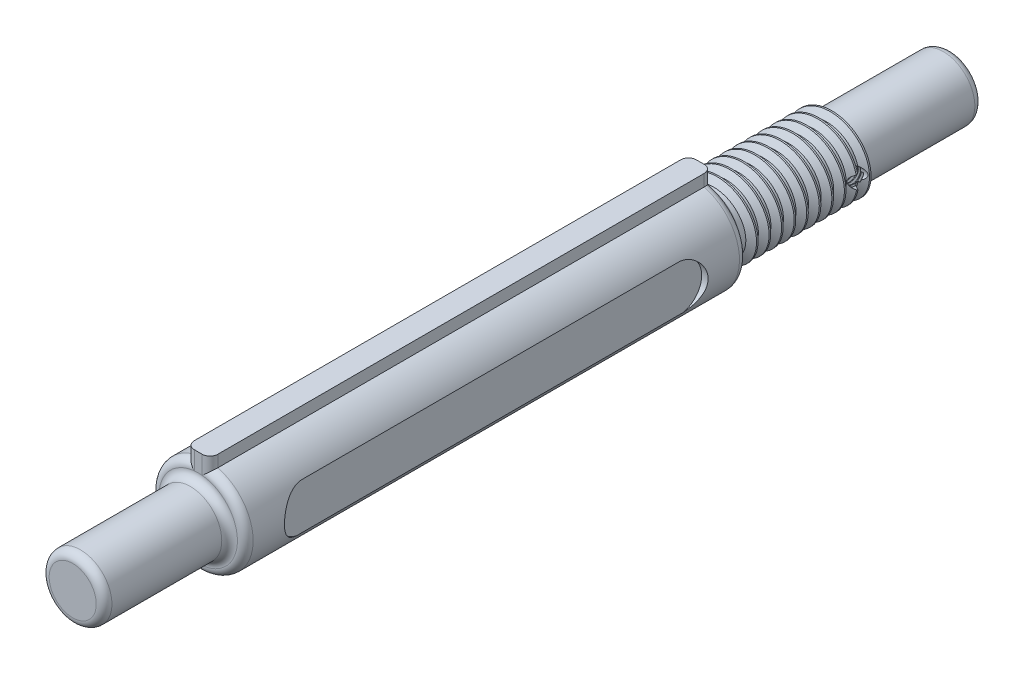
SolidWorks part; units mm, degrees
material "AISI 1020"
ref_plane "Front Plane" through (0, 0, 0) normal (0, 0, 1) x (1, 0, 0)
ref_plane "Top Plane" through (0, 0, 0) normal (0, 1, 0) x (1, 0, 0)
ref_plane "Right Plane" through (0, 0, 0) normal (1, 0, 0) x (0, 0, -1)
sketch "Sketch1" plane through (0, 0, 0) normal (0, 0, 1) x (1, 0, 0)
  line L0 (-1.1906, 4.6113) -> (-1.1906, 5.8019)
  line L1 (-1.1906, 5.8019) -> (1.1906, 5.8019)
  line L2 (1.1906, 5.8019) -> (1.1906, 4.6113)
  arc A1 (-1.1906, 4.6113) -> (1.1906, 4.6113) centre (0, 0) ccw
  point P2 (0, 5.8019)
  dimension "D1" = 4.7625
  dimension "D2" = 1.1906
  dimension "D3" = 2.3813
extrude "Boss-Extrude1" add sketch "Sketch1" along normal blind 50.8
sketch "Sketch2" plane through (0, 0, 50.8) normal (0, 0, 1) x (1, 0, 0)
  circle A0 centre (0, 0) radius 3.175
  dimension "D1" = 6.35
extrude "Boss-Extrude2" add sketch "Sketch2" along normal blind 12.7
fillet "Fillet2" radius 0.7937 4 edges at (1.1906, 5.2066, 0) (-1.1906, 5.2066, 0) (1.1906, 5.2066, 50.8) (-1.1906, 5.2066, 50.8)
fillet "Fillet4" radius 0.7937 2 edges at (0, -4.7625, 50.8) (3.175, 0, 50.8)
sketch "Sketch3" plane through (0, 0, 0) normal (0, 0, -1) x (-1, 0, 0)
  circle A0 centre (0, 0) radius 3.175
  dimension "D1" = 6.35
extrude "Boss-Extrude3" add sketch "Sketch3" along normal blind 25.4
fillet "Fillet5" radius 0.7937 2 edges at (0, -4.7625, 0) (3.175, 0, 0)
ref_plane "Plane1" through (5.9531, 0, 0) normal (1, 0, 0) x (0, 0, -1)
sketch "Sketch4" plane through (5.9531, 0, 0) normal (1, 0, 0) x (0, 0, -1)
  line L0 (-50.0062, -0.0756) -> (-0.7938, -0.0756) construction
  line L1 (-50.0062, 4.6113) -> (-50.0062, -4.7625) construction
  line L2 (-0.7938, -4.7625) -> (-0.7938, 4.6113) construction
  line L3 (-44.45, -0.0756) -> (-6.35, -0.0756) construction
  line L4 (-44.45, 2.3056) -> (-6.35, 2.3056)
  line L5 (-44.45, -2.4569) -> (-6.35, -2.4569)
  arc A0 (-44.45, 2.3056) -> (-44.45, -2.4569) centre (-44.45, -0.0756) ccw
  arc A1 (-6.35, -2.4569) -> (-6.35, 2.3056) centre (-6.35, -0.0756) ccw
  point P8 (-25.4, -0.0756)
  point P13 (-25.4, -0.0756)
  dimension "D1" = 2.3813
  dimension "D2" = 19.05
extrude "Cut-Extrude1" cut sketch "Sketch4" against normal blind 1.8415
thread "Thread2" pitch 1.27 method extrude profile "Thread Profile2" start angle 0, offset 0, length 0, pitch 1.27, diameter 6.35
ref_plane "Plane3" through (-3.175, 0, -0.7937) normal (0, -1, 0) x (-1, 0, 0)
sketch "Thread Profile2" plane through (-3.175, 0, -0.7937) normal (0, -1, 0) x (-1, 0, 0)
  line L0 (0, 0) -> (0, 1.27) construction
  line L1 (0, 0) -> (0.6874, 0.3969)
  line L2 (0.6874, 0.3969) -> (0.6874, 0.5556)
  line L3 (0.6874, 0.5556) -> (0, 0.9525)
  line L4 (0.6874, 0.4762) -> (0, 0.4762) construction
  line L11 (0, 0) -> (0, 0.9525)
  point P2 (0, 0)
  dimension "Pitch" = 1.27
  dimension "Profile_Angle" = 60
  dimension "Profile_Land" = 0.1588
  dimension "Profile_Height" = 0.6874
sketch "Sketch6" plane through (5.9531, 0, 0) normal (1, 0, 0) x (0, 0, -1)
  line L0 (-0.7938, 4.6113) -> (-0.7938, -4.7625) construction
  circle A0 centre (12.4142, -0.0756) radius 0.7937
  point P6 (-0.7938, -0.0756)
  dimension "D1" = 1.5875
  dimension "D2" = 13.208
extrude "Cut-Extrude2" cut sketch "Sketch6" against normal blind 4.445
thread "Thread1" pitch 0.3175 method cut profile "Thread Profile1" start angle 0, offset 0, length 0, pitch 0.3175, diameter 1.5875
ref_plane "Plane2" through (1.5081, -0.0756, -13.208) normal (0, -1, 0) x (0, 0, -1)
sketch "Thread Profile1" plane through (1.5081, -0.0756, -13.208) normal (0, -1, 0) x (0, 0, -1)
  line L0 (0, 0) -> (0, 0.3175) construction
  line L1 (0, 0) -> (0.1719, 0.0992)
  line L2 (0.1719, 0.0992) -> (0.1719, 0.1389)
  line L3 (0.1719, 0.1389) -> (0, 0.2381)
  line L4 (0.1719, 0.1191) -> (0, 0.1191) construction
  line L11 (0, 0) -> (0, 0.2381)
  point P2 (0, 0)
  dimension "Pitch" = 0.3175
  dimension "Profile_Angle" = 60
  dimension "Profile_Land" = 0.0397
  dimension "Profile_Height" = 0.1719
fillet "Fillet6" radius 0.7937 2 edges at (3.175, 0, 63.5) (-3.175, 0, -25.4)
